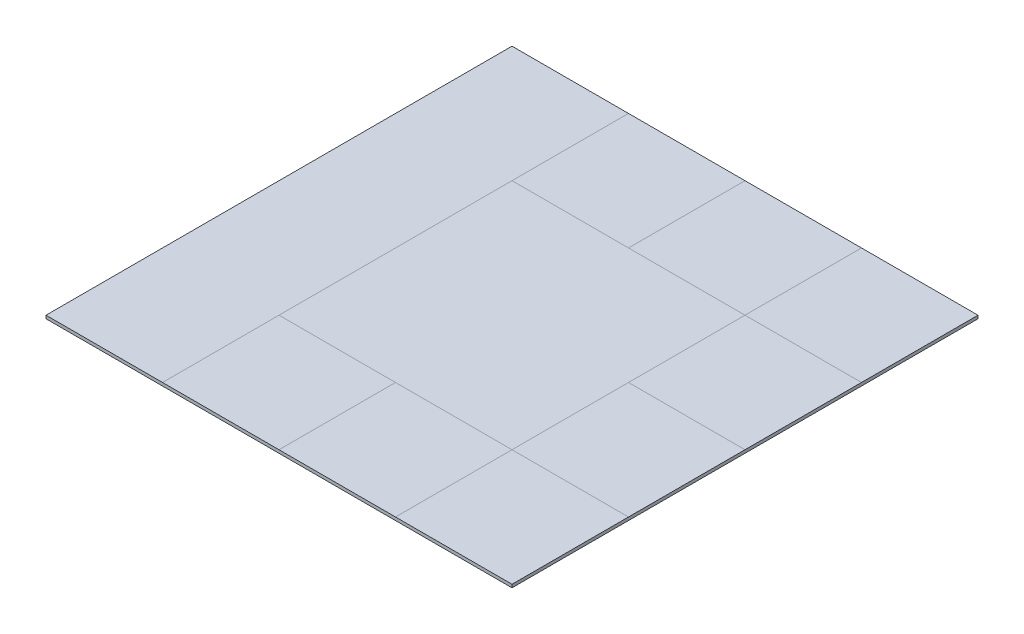
SolidWorks part; units mm, degrees
ref_plane "Front Plane" through (0, 0, 0) normal (0, 0, 1) x (1, 0, 0)
ref_plane "Top Plane" through (0, 0, 0) normal (0, 1, 0) x (1, 0, 0)
ref_plane "Right Plane" through (0, 0, 0) normal (1, 0, 0) x (0, 0, -1)
sketch "Sketch1" plane through (0, 0, 0) normal (0, 1, 0) x (1, 0, 0)
  line L0 (375, -375) -> (750, -750) construction
  line L1 (-750, -750) -> (750, -750)
  line L2 (-750, -750) -> (-750, 750)
  line L3 (-750, 750) -> (750, 750)
  line L4 (750, -750) -> (750, 750)
  line L5 (-750, -750) -> (-375, -375) construction
  line L6 (-750, 750) -> (-375, 375) construction
  line L7 (-375, -750) -> (375, -750)
  line L8 (-375, -750) -> (-375, 750)
  line L9 (-375, 750) -> (375, 750)
  line L10 (375, -750) -> (375, -375)
  line L20 (-750, 442.3995) -> (-750, -307.6005)
  line L27 (375, 375) -> (750, 375)
  line L28 (-750, 375) -> (-750, -375)
  line L29 (375, -375) -> (750, -375)
  line L30 (750, 375) -> (750, -375)
  line L31 (375, 375) -> (750, 750) construction
  line L32 (375, 375) -> (375, 750)
  point P0 (0, 0)
  point P10 (750, 0)
  point P11 (0, 750)
  dimension "D1" = 1500
  dimension "D2" = 750
extrude "Boss-Extrude1" add sketch "Sketch1" along normal blind 10 contours L1 L8 L3 L2 L20 | L27 L32 L3 L8 L1 L10 L29 L4 | L29 L10 L1 L4 | L32 L27 L4 L3 region at (-562.5, 0, 0) region at (112.5, 0, 0) region at (562.5, 0, 562.5) region at (562.5, 0, -562.5)
split line "Split Line5"
sketch "Sketch1<7>" plane through (0, 0, 0) normal (0, 1, 0) x (1, 0, 0) same geometry as "Sketch1"
ref_plane "Plane1" through (-750, 10, -750) normal (1, 0, 0) x (0, 0, -1)
sketch "Sketch4" plane through (0, 10, 0) normal (0, 1, 0) x (1, 0, 0)
  line L0 (0, 750) -> (0, 375)
  line L1 (-375, 750) -> (375, 750) construction
  line L2 (0, 375) -> (-375, 375)
  line L3 (-375, -750) -> (-375, 750) construction
split line "Split Line9"
sketch "Sketch5" plane through (0, 10, 0) normal (0, 1, 0) x (1, 0, 0)
  line L0 (0, 375) -> (375, 375)
  line L1 (375, 375) -> (375, -375)
  line L2 (375, -375) -> (-375, -375)
  line L3 (-375, -750) -> (-375, 375) construction
split line "Split Line10"
sketch "Sketch6" plane through (0, 10, 0) normal (0, 1, 0) x (1, 0, 0)
  line L0 (0, -375) -> (0, -750)
  line L1 (-375, -375) -> (375, -375) construction
  line L2 (-375, -750) -> (375, -750) construction
  line L3 (375, 0) -> (750, 0)
  line L4 (375, -375) -> (375, 375) construction
  line L5 (750, -375) -> (750, 375) construction
split line "Split Line11"
equation "\"Scale\"= 8"
equation "\"Tile Size\"= \"Road Size\" * 2"
equation "\"D1@Sketch1\"=\"Tile Size\""
equation "\"Road Size\"= \"Real Lane Size\" * 2 / \"Scale\""
equation "\"D2@Sketch1\"=\"Road Size\""
equation "\"Real Lane Size\"= 3m"
